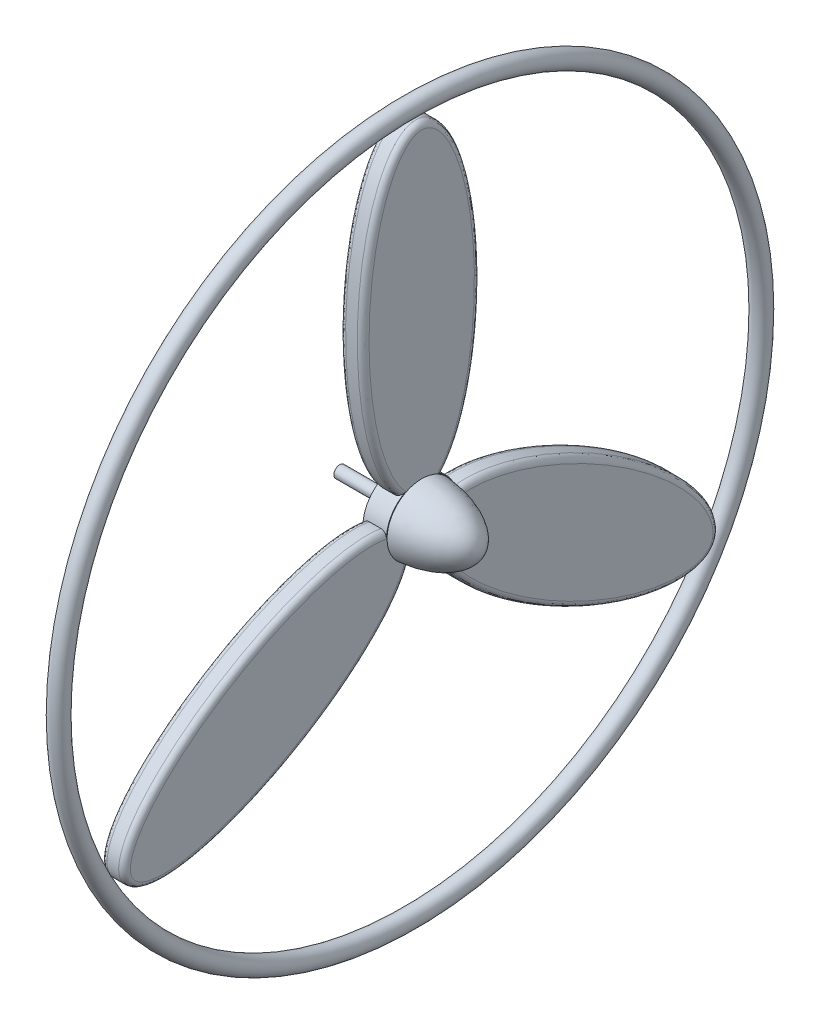
SolidWorks part; units mm, degrees
ref_plane "Front Plane" through (0, 0, 0) normal (0, 0, 1) x (1, 0, 0)
ref_plane "Top Plane" through (0, 0, 0) normal (0, 1, 0) x (1, 0, 0)
ref_plane "Right Plane" through (0, 0, 0) normal (1, 0, 0) x (0, 0, -1)
sketch "Sketch1" plane through (0, 0, 0) normal (0, 0, 1) x (1, 0, 0)
  line L0 (-176.1899, 0) -> (191.3183, 0) construction
  circle A0 centre (0, 60) radius 1.5
  dimension "D1" = 3
  dimension "D2" = 60
revolve "Revolve2" add sketch "Sketch1" angle 360 about L0
sketch "Sketch3" plane through (0, 0, 0) normal (1, 0, 0) x (0, 0, -1)
  line L0 (0, 0) -> (0, 151.028) construction
  circle A2 centre (0, 0) radius 58.5 construction
  arc A9 (-3.5923, 4.8418) -> (-5.9418, 1.0209) centre (0, 0) ccw
  arc A10 (-2.0867, -5.6562) -> (2.0867, -5.6562) centre (0, 0) ccw
  arc A11 (5.9418, 1.0209) -> (3.5923, 4.8418) centre (0, 0) ccw
  ellipse E0 centre (0, 30.7445) end of major axis (0, 2.9891) minor radius 10 (3.5923, 4.8418) -> (-3.5923, 4.8418) ccw
  ellipse E1 centre (26.1925, -15.1223) end of major axis (50.2295, -29) minor radius 9.9981 (2.0867, -5.6562) -> (5.9418, 1.0209) ccw
  ellipse E2 centre (-26.1925, -15.1223) end of major axis (-50.2295, -29) minor radius 9.9981 (-5.9418, 1.0209) -> (-2.0867, -5.6562) ccw
  point P26 (0, 0)
  point P29 (0, 0)
  dimension "D2" = 20
extrude "Boss-Extrude1" add sketch "Sketch3" along normal blind 2 and the other way blind 2 separate body
sketch "Sketch5" plane through (0, 0, 0) normal (0, 0, 1) x (1, 0, 0)
  line L0 (-19.8335, 0) -> (15.5198, 0) construction
  line L2 (0, 6) -> (0, 0)
  line L3 (0, 0) -> (12, 0)
  ellipse E0 centre (0, 0) end of major axis (-12, 0) minor radius 6 (12, 0) -> (0, 6) ccw
  dimension "D1" = 6
  dimension "D2" = 12
revolve "Revolve4" add sketch "Sketch5" angle 360 about L0
fillet "Fillet3" radius 1 6 edges at (-2, 58.5, 0) (2, 58.5, 0) (-2, -29, 50.2295) (2, -29, 50.2295) (-2, -29, -50.2295) (2, -29, -50.2295)
sketch "Sketch6" plane through (-2, 0, 0) normal (-1, 0, 0) x (0, 0, 1)
  circle A0 centre (0, 0) radius 1
  dimension "D1" = 2
extrude "Boss-Extrude2" add sketch "Sketch6" along normal blind 10
